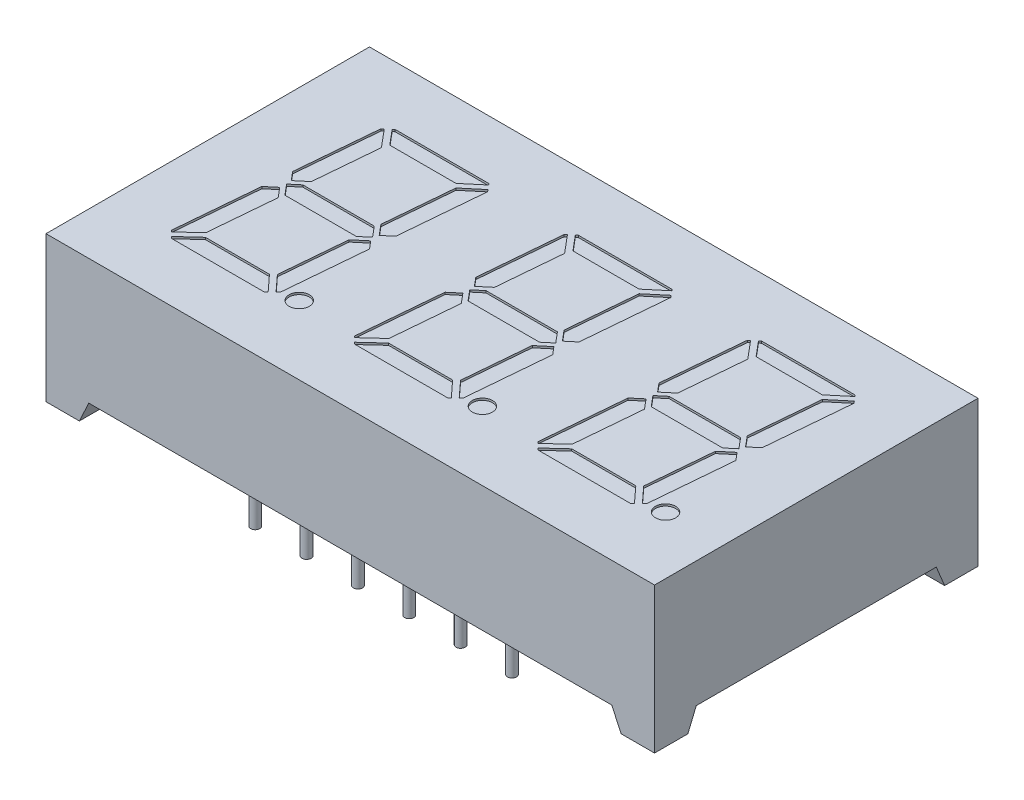
SolidWorks part; units mm, degrees
ref_plane "Front Plane" through (0, 0, 0) normal (0, 0, 1) x (1, 0, 0)
ref_plane "Top Plane" through (0, 0, 0) normal (0, 1, 0) x (1, 0, 0)
ref_plane "Right Plane" through (0, 0, 0) normal (1, 0, 0) x (0, 0, -1)
sketch "Sketch1" plane through (0, 0, 0) normal (0, 1, 0) x (1, 0, 0)
  line L0 (-15.05, 8) -> (15.05, -8) construction
  line L1 (-15.05, 8) -> (15.05, 8)
  line L2 (-15.05, 8) -> (-15.05, -8)
  line L3 (-15.05, -8) -> (15.05, -8)
  line L4 (15.05, 8) -> (15.05, -8)
  dimension "D1" = 30.1
  dimension "D2" = 16
extrude "Extrude1" add sketch "Sketch1" against normal blind 7.2 contours L3 L4 L1 L2
sketch "Sketch6" plane through (0, 0, 0) normal (0, 1, 0) x (-1, 0, 0)
  line L0 (1.8994, -5.0318) -> (1.8181, -5.1)
  line L1 (-2.771, -0.5413) -> (-3.1364, -4.7178)
  line L3 (1.8994, -5.0318) -> (1.2801, -4.2937)
  line L4 (-2.873, -5.0318) -> (-1.9934, -4.2937)
  line L6 (0, 0) -> (0, -8) construction
  line L7 (1.7298, 0.4435) -> (-1.804, 0.4435)
  line L10 (1.3798, -3.9813) -> (1.6587, -0.7925)
  line L12 (-1.804, -0.4435) -> (-2.2407, 0.077)
  line L13 (-2.8157, -5.1) -> (1.8181, -5.1)
  line L14 (-1.2767, 4.2131) -> (-2.0083, 5.0115)
  line L15 (-1.893, -0.6824) -> (-2.1919, -4.0985)
  line L16 (-1.4811, 4.0258) -> (-2.2045, 4.8153)
  line L17 (2.0788, 4.0087) -> (2.9625, 4.8185)
  line L18 (3.0338, 4.7472) -> (2.9625, 4.8185)
  line L20 (-2.3489, 0.2758) -> (-2.6664, 0.6542)
  line L21 (2.1117, -4.8536) -> (1.3798, -3.9813)
  line L22 (-1.4811, 4.0258) -> (-1.7664, 0.7645)
  line L23 (-3.0511, -4.8195) -> (-3.1364, -4.7178)
  line L25 (-2.2407, 0.077) -> (-1.804, 0.4435)
  line L26 (2.1984, -0.3397) -> (2.5519, -0.761)
  line L27 (1.8915, 4.2131) -> (2.7663, 5.0147)
  line L28 (2.2003, -4.7793) -> (2.5519, -0.761)
  line L29 (1.6587, -0.7925) -> (2.1984, -0.3397)
  line L31 (2.1938, 0.2354) -> (2.6743, 0.6385)
  line L32 (1.7298, -0.4435) -> (-1.804, -0.4435)
  line L33 (1.8915, 4.2131) -> (-1.2767, 4.2131)
  line L34 (2.1665, -0.077) -> (1.7298, 0.4435)
  line L35 (-2.3253, -0.1672) -> (-1.893, -0.6824)
  line L36 (2.7663, 5.0147) -> (2.681, 5.1)
  line L37 (-3.0511, -4.8195) -> (-2.1919, -4.0985)
  line L38 (-2.8157, -5.1) -> (-2.873, -5.0318)
  line L39 (2.681, 5.1) -> (-1.9198, 5.1)
  line L40 (-2.3253, -0.1672) -> (-2.771, -0.5413)
  line L41 (2.6743, 0.6385) -> (3.0338, 4.7472)
  line L42 (-2.3118, 4.708) -> (-2.6664, 0.6542)
  line L43 (-1.7664, 0.7645) -> (-2.3489, 0.2758)
  line L44 (-1.9198, 5.1) -> (-2.0083, 5.0115)
  line L46 (1.7298, -0.4435) -> (2.1665, -0.077)
  line L48 (2.2003, -4.7793) -> (2.1117, -4.8536)
  line L49 (-1.9934, -4.2937) -> (1.2801, -4.2937)
  line L52 (2.1938, 0.2354) -> (1.7907, 0.7158)
  line L53 (1.7907, 0.7158) -> (2.0788, 4.0087)
  line L54 (-2.2045, 4.8153) -> (-2.3118, 4.708)
  line L65 (0, 0) -> (15.05, 0) construction
  line L81 (0, 0) -> (0, -8) construction
  circle A0 centre (-3.1364, 4.6011) radius 0.4989
  point P4 (0, -7.7933)
  point P5 (0, 0)
  point P6 (0, 0)
extrude "Cut-Extrude1" cut sketch "Sketch6" against normal blind 0.1
sketch "Sketch12" plane through (-15.05, 0, 0) normal (-1, 0, 0) x (0, 0, 1)
  line L0 (-6.35, -7.2) -> (-5.9358, -6.2)
  line L1 (-5.9358, -6.2) -> (5.9358, -6.2)
  line L2 (5.9358, -6.2) -> (6.35, -7.2)
  line L4 (0, -3.96) -> (0, 3.96) construction
  line L5 (-8, -7.2) -> (8, -7.2) construction
  point P2 (0, -6.2)
  dimension "D1" = 1
  dimension "D2" = 45
  dimension "D3" = 12.7
extrude "Cut-Extrude2" cut sketch "Sketch12" against normal through all and the other way through all flip side to cut
sketch "Sketch13" plane through (0, 0, -8) normal (0, 0, -1) x (-1, 0, 0)
  line L0 (-13.4, -7.2) -> (-12.9337, -6.2)
  line L1 (15.05, -7.2) -> (-15.05, -7.2) construction
  line L2 (-12.9337, -6.2) -> (12.9337, -6.2)
  line L3 (12.9337, -6.2) -> (13.4, -7.2)
  line L4 (0, 3.96) -> (0, -3.96) construction
  line L5 (15.05, -6.2) -> (-15.05, -6.2) construction
  point P4 (0, -6.2)
  dimension "D1" = 26.8
  dimension "D2" = 50
extrude "Cut-Extrude3" cut sketch "Sketch13" against normal through all and the other way through all flip side to cut
pattern_linear "LPattern1" count 2 spacing 9.06 along (1, 0, 0) of "Cut-Extrude1"
pattern_linear "LPattern2" count 2 spacing 9.06 along (-1, 0, 0) of "Cut-Extrude1"
sketch "Sketch11" plane through (0, -7.2, 0) normal (0, -1, 0) x (1, 0, 0)
  line L0 (0, -3.96) -> (0, 3.96) construction
  line L1 (3.96, 0) -> (-3.96, 0) construction
  circle A0 centre (6.35, 6.35) radius 0.225
  dimension "D2" = 0.45
  dimension "D1" = 6.35
  dimension "D3" = 6.35
extrude "Boss-Extrude4" add sketch "Sketch11" along normal blind 1.8 and the other way up to next
pattern_linear "LPattern3" count 6 spacing 2.54 along (-1, 0, 0) count 2 spacing 12.7 along (0, 0, -1) of "Boss-Extrude4"
